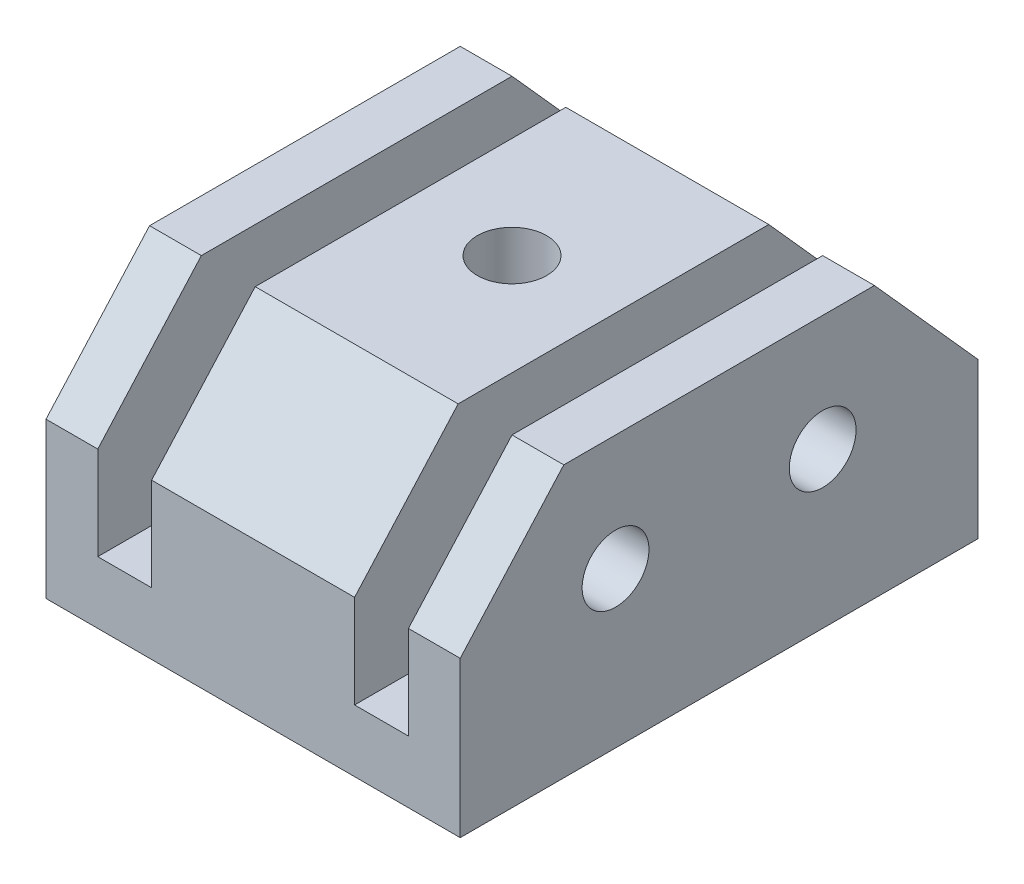
SolidWorks part; units mm, degrees
ref_plane "Front Plane" through (0, 0, 0) normal (0, 0, 1) x (1, 0, 0)
ref_plane "Top Plane" through (0, 0, 0) normal (0, 1, 0) x (1, 0, 0)
ref_plane "Right Plane" through (0, 0, 0) normal (1, 0, 0) x (0, 0, -1)
sketch "Sketch1" plane through (0, 0, 0) normal (1, 0, 0) x (0, 0, -1)
  line L1 (0, 0) -> (63.5, 0)
  line L2 (0, 0) -> (0, 6.35)
  line L3 (0, 6.35) -> (63.5, 6.35)
  line L4 (63.5, 0) -> (63.5, 6.35)
  dimension "D1" = 6.35
  dimension "D2" = 63.5
extrude "Boss-Extrude1" add sketch "Sketch1" against normal blind 50.8
sketch "Sketch2" plane through (0, 0, 0) normal (1, 0, 0) x (0, 0, -1)
  line L0 (0, 6.35) -> (0, 19.05)
  line L1 (0, 19.05) -> (12.7, 33.249)
  line L2 (12.7, 33.249) -> (50.8, 33.249)
  line L3 (50.8, 33.249) -> (63.5, 19.05)
  line L4 (63.5, 19.05) -> (63.5, 6.35)
  line L5 (63.5, 6.35) -> (0, 6.35)
  point P7 (31.75, 33.249)
  point P10 (31.75, 6.35)
  dimension "D1" = 38.1
  dimension "D2" = 12.7
  dimension "D3" = 12.7
  dimension "D4" = 19.05
  dimension "D5" = 19.05
extrude "Boss-Extrude2" add sketch "Sketch2" against normal blind 50.8
sketch "Sketch10" plane through (0, 0, -63.5) normal (0, 0, -1) x (-1, 0, 0)
  line L1 (50.8, 33.249) -> (0, 33.249) construction
  line L3 (6.35, 7.62) -> (6.35, 33.249)
  line L4 (6.35, 33.249) -> (12.954, 33.249)
  line L5 (12.954, 7.62) -> (12.954, 33.249)
  line L6 (6.35, 7.62) -> (12.954, 7.62)
  line L8 (50.8, 0) -> (0, 0) construction
  point P11 (12.954, 7.62)
  dimension "D1" = 7.62
  dimension "D2" = 6.604
  dimension "D3" = 6.35
extrude "Cut-Extrude1" cut sketch "Sketch10" against normal through all
pattern_linear "LPattern3" count 2 spacing 31.496 along (-1, 0, 0) of "Cut-Extrude1"
sketch "Sketch11" plane through (0, 0, 0) normal (1, 0, 0) x (0, 0, -1)
  circle A0 centre (19.05, 19.05) radius 4.0957
  circle A1 centre (19.05, 19.05) radius 7.9375 construction
  circle A2 centre (44.45, 19.05) radius 4.0958
  circle A3 centre (44.45, 19.05) radius 7.9375 construction
  dimension "D1" = 8.1915
  dimension "D3" = 15.875
  dimension "D4" = 8.1915
  dimension "D6" = 15.875
  dimension "D2" = 6.35
  dimension "D5" = 6.35
extrude "Cut-Extrude2" cut sketch "Sketch11" against normal through all
sketch "Sketch14" plane through (0, 33.249, 0) normal (0, 1, 0) x (1, 0, 0)
  line L3 (-37.846, 12.7) -> (-37.846, 50.8) construction
  point P0 (-25.4, 31.75)
  point P4 (-37.846, 31.75)
  dimension "D1" = 12.446
sketch "Sketch17" plane through (0, 40.0201, -44.7438) normal (0, 0.6667, -0.7454) x (-1, 0, 0)
  line L0 (12.954, -28.1343) -> (12.954, -9.0843) construction
  line L1 (37.846, -9.0843) -> (12.954, -9.0843) construction
  point P0 (25.4, -18.6093)
  point P4 (12.954, -18.6093)
  point P7 (25.4, -9.0843)
sketch "Sketch18" plane through (0, 8.4667, 9.466) normal (0, 0.6667, 0.7454) x (1, 0, 0)
  line L0 (-12.954, 33.249) -> (-12.954, 14.199) construction
  line L1 (-37.846, 33.249) -> (-12.954, 33.249) construction
  point P0 (-25.4, 23.724)
  point P1 (-25.4, 23.724)
  point P4 (-12.954, 23.724)
  point P7 (-25.4, 33.249)
ref_plane "Plane2" through (0, 33.02, 0) normal (0, -1, 0) x (-1, 0, 0)
fillet "Fillet1" [suppressed] radius 2.54
sketch "Sketch19" plane through (0, 0, 0) normal (0, -1, 0) x (1, 0, 0)
  line L0 (-24.6552, -63.5) -> (-24.6552, 0) construction
  line L1 (-50.8, -63.5) -> (0, -63.5) construction
  line L2 (-50.8, 0) -> (0, 0) construction
  line L3 (0, -31.75) -> (-50.8, -31.75) construction
  line L4 (0, 0) -> (0, -63.5) construction
  line L5 (-50.8, 0) -> (-50.8, -63.5) construction
  line L7 (-3.4052, -53) -> (-45.9052, -53)
  line L8 (-3.4052, -53) -> (-3.4052, -10.5)
  line L9 (-3.4052, -10.5) -> (-45.9052, -10.5)
  line L10 (-45.9052, -53) -> (-45.9052, -10.5)
  line L11 (-3.4052, -53) -> (-45.9052, -10.5) construction
  line L12 (-3.4052, -10.5) -> (-45.9052, -53) construction
  point P12 (-24.6552, -31.75)
  dimension "D1" = 42.5
extrude "Cut-Extrude3" cut sketch "Sketch19" against normal blind 5.08
sketch "Sketch21" plane through (0, 0, 0) normal (0, -1, 0) x (1, 0, 0)
  line L0 (-25.4, -63.5) -> (-25.4, 0) construction
  line L1 (-50.8, -63.5) -> (0, -63.5) construction
  line L2 (-50.8, 0) -> (0, 0) construction
  line L3 (-50.8, -31.75) -> (0, -31.75) construction
  line L4 (-50.8, 0) -> (-50.8, -63.5) construction
  line L5 (0, 0) -> (0, -63.5) construction
  circle A0 centre (-40.9, -47.25) radius 1.7
  circle A1 centre (-40.9, -16.25) radius 1.7
  circle A2 centre (-9.9, -16.25) radius 1.7
  circle A3 centre (-9.9, -47.25) radius 1.7
  point P14 (-25.4, -31.75)
  point P24 (-25.4, -31.75)
  dimension "D1" = 3.4
  dimension "D3" = 15.5
  dimension "D2" = 15.5
  dimension "D4" = 4
extrude "Cut-Extrude4" cut sketch "Sketch21" against normal up to next
sketch "Sketch22" plane through (0, 0, 0) normal (0, -1, 0) x (1, 0, 0)
  line L1 (-25.4, -63.5) -> (-25.4, 0) construction
  line L2 (-50.8, -63.5) -> (0, -63.5) construction
  line L3 (-50.8, 0) -> (0, 0) construction
  line L4 (0, -31.75) -> (-50.8, -31.75) construction
  line L6 (0, 0) -> (0, -63.5) construction
  line L7 (-50.8, 0) -> (-50.8, -63.5) construction
  circle A1 centre (-25.4, -31.75) radius 11
  dimension "D1" = 22
extrude "Cut-Extrude5" cut sketch "Sketch22" against normal blind 3 from surface starting at face at (-9.9, 5.08, -48.95)
sketch "Sketch23" plane through (0, 0, 0) normal (0, -1, 0) x (1, 0, 0)
  circle A0 centre (-25.4, -31.75) radius 4.25
extrude "Cut-Extrude6" cut sketch "Sketch23" against normal through all
